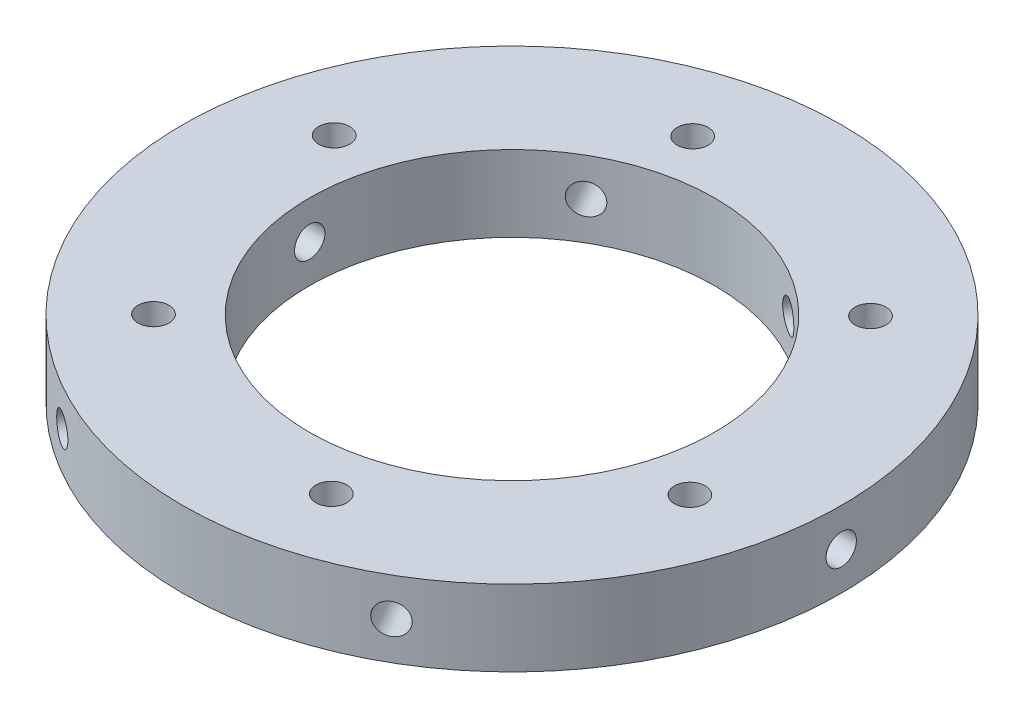
SolidWorks part; units mm, degrees
ref_plane "Front Plane" through (0, 0, 0) normal (0, 0, 1) x (1, 0, 0)
ref_plane "Top Plane" through (0, 0, 0) normal (0, 1, 0) x (1, 0, 0)
ref_plane "Right Plane" through (0, 0, 0) normal (1, 0, 0) x (0, 0, -1)
sketch "Sketch1" plane through (0, 0, 0) normal (0, 1, 0) x (1, 0, 0)
  line L0 (0, 0) -> (0, 87.698) construction
  line L1 (0, 0) -> (-128.1213, 0) construction
  circle A0 centre (0, 0) radius 65
  circle A1 centre (0, 0) radius 40
  circle A2 centre (12.723, -48.3542) radius 3.05
  dimension "D1" = 130
  dimension "D2" = 80
extrude "Boss-Extrude1" add sketch "Sketch1" along normal blind 15
sketch "Sketch2" plane through (0, 0, 0) normal (1, 0, 0) x (0, 0, -1)
  line L0 (65, 7.5) -> (-65, 7.5) construction
  line L1 (65, 0) -> (65, 15) construction
  line L2 (-65, 15) -> (-65, 0) construction
  circle A0 centre (0, 7.5) radius 3
  dimension "D1" = 6
extrude "Cut-Extrude1" cut sketch "Sketch2" against normal through all
pattern_circular "CirPattern1" count 6 over 360 about axis through (0, 15, 0) along (0, 1, 0) of "Cut-Extrude1"
pattern_circular "CirPattern2" count 6 every 60 about axis through (0, 15, 0) along (0, 1, 0) of face at (12.723, 15, 51.4042)
equation "\"holes\"=6"
equation "\"D1@CirPattern1\"=\"holes\""
